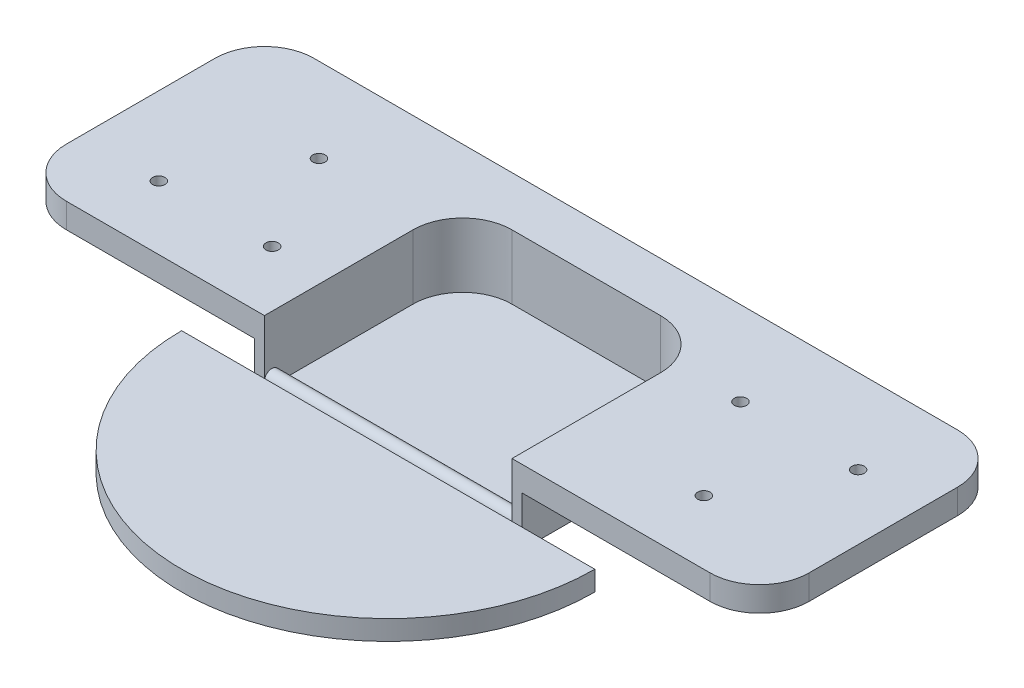
SolidWorks part; units mm, degrees
ref_plane "Front Plane" through (0, 0, 0) normal (0, 0, 1) x (1, 0, 0)
ref_plane "Top Plane" through (0, 0, 0) normal (0, 1, 0) x (1, 0, 0)
ref_plane "Right Plane" through (0, 0, 0) normal (1, 0, 0) x (0, 0, -1)
sketch "Sketch1" plane through (0, 0, 0) normal (0, 1, 0) x (1, 0, 0)
  line L1 (325, -125) -> (-325, -125)
  line L2 (375, -75) -> (375, 75)
  line L3 (325, 125) -> (-325, 125)
  line L4 (-375, -75) -> (-375, 75)
  line L5 (375, -125) -> (-375, 125) construction
  line L6 (375, 125) -> (-375, -125) construction
  arc A0 (325, -125) -> (375, -75) centre (325, -75) ccw
  arc A1 (375, 75) -> (325, 125) centre (325, 75) ccw
  arc A2 (-325, -125) -> (-375, -75) centre (-325, -75) cw
  arc A3 (-325, 125) -> (-375, 75) centre (-325, 75) ccw
  point P0 (0, 0)
  dimension "D3" = 50
  dimension "D1" = 750
  dimension "D2" = 250
extrude "Boss-Extrude1" add sketch "Sketch1" against normal blind 75
sketch "Sketch2" plane through (0, 0, 0) normal (0, 1, 0) x (1, 0, 0)
  line L0 (-325, -125) -> (325, -125) construction
  line L1 (125, -125) -> (-125, -125)
  line L2 (125, -125) -> (125, 25)
  line L3 (75, 75) -> (-75, 75)
  line L4 (-125, -125) -> (-125, 25)
  line L5 (0, 0) -> (125, 0) construction
  arc A0 (125, 25) -> (75, 75) centre (75, 25) ccw
  arc A1 (-75, 75) -> (-125, 25) centre (-75, 25) ccw
  point P11 (125, 75)
  point P14 (-125, 75)
  dimension "D4" = 50
  dimension "D1" = 200
  dimension "D2" = 250
  dimension "D3" = 125
extrude "Cut-Extrude1" cut sketch "Sketch2" against normal blind 65
shell "Shell1" thickness 10 removed face at (0, -75, 0)
sketch "Sketch5" plane through (0, -75, 0) normal (0, -1, 0) x (1, 0, 0)
  line L3 (135, 115) -> (325, 115) construction
  line L4 (325, 125) -> (-325, 125)
  line L5 (-375, 75) -> (-375, -75)
  line L6 (-325, -125) -> (325, -125)
  line L7 (375, -75) -> (375, 75)
  line L8 (325, 125) -> (-325, 125)
  line L9 (-375, 75) -> (-375, -75)
  line L10 (-325, -125) -> (325, -125)
  line L11 (375, -75) -> (375, 75)
  line L12 (365, 75) -> (365, -75) construction
  line L13 (325, -115) -> (-325, -115) construction
  line L14 (-365, -75) -> (-365, 75) construction
  line L15 (-325, 115) -> (-135, 115) construction
  line L19 (135, 115) -> (325, 115)
  line L20 (365, 75) -> (365, -75)
  line L21 (325, -115) -> (-325, -115)
  line L22 (-365, -75) -> (-365, 75)
  line L23 (-325, 115) -> (-135, 115)
  line L24 (135, 115) -> (135, 125)
  line L25 (-135, 115) -> (-135, 125)
  arc A0 (325, -115) -> (365, -75) centre (325, -75) ccw construction
  arc A3 (365, 75) -> (325, 115) centre (325, 75) ccw construction
  arc A4 (375, 75) -> (325, 125) centre (325, 75) ccw
  arc A5 (-325, 125) -> (-375, 75) centre (-325, 75) ccw
  arc A6 (-375, -75) -> (-325, -125) centre (-325, -75) ccw
  arc A7 (325, -125) -> (375, -75) centre (325, -75) ccw
  arc A8 (375, 75) -> (325, 125) centre (325, 75) ccw
  arc A9 (-325, 125) -> (-375, 75) centre (-325, 75) ccw
  arc A10 (-375, -75) -> (-325, -125) centre (-325, -75) ccw
  arc A11 (325, -125) -> (375, -75) centre (325, -75) ccw
  arc A12 (-365, -75) -> (-325, -115) centre (-325, -75) ccw construction
  arc A13 (-325, 115) -> (-365, 75) centre (-325, 75) ccw construction
  arc A14 (325, -115) -> (365, -75) centre (325, -75) ccw
  arc A17 (365, 75) -> (325, 115) centre (325, 75) ccw
  arc A18 (-365, -75) -> (-325, -115) centre (-325, -75) ccw
  arc A19 (-325, 115) -> (-365, 75) centre (-325, 75) ccw
  arc M23 (375, 75) -> (325, 125) centre (325, 75) ccw
  line M24 (325, 125) -> (-325, 125)
  arc M25 (-325, 125) -> (-375, 75) centre (-325, 75) ccw
  line M26 (-375, 75) -> (-375, -75)
  arc M27 (-375, -75) -> (-325, -125) centre (-325, -75) ccw
  line M28 (-325, -125) -> (325, -125)
  arc M29 (325, -125) -> (375, -75) centre (325, -75) ccw
  line M30 (375, -75) -> (375, 75)
  line M36 (135, 115) -> (325, 115)
  arc M37 (325, 115) -> (365, 75) centre (325, 75) cw
  line M38 (365, 75) -> (365, -75)
  arc M39 (365, -75) -> (325, -115) centre (325, -75) cw
  line M40 (325, -115) -> (-325, -115)
  arc M41 (-325, -115) -> (-365, -75) centre (-325, -75) cw
  line M42 (-365, -75) -> (-365, 75)
  arc M43 (-365, 75) -> (-325, 115) centre (-325, 75) cw
  line M44 (-325, 115) -> (-135, 115)
  dimension "D1" = 0
extrude "Cut-Extrude3" cut sketch "Sketch5" against normal blind 50 contours L25 L24 M44 M24 M25 M26 M27 M28 M29 M30 M23 M36 M37 M38 M39 M40 M41 M42 M43 region at (354.7652, -75, 104.7652)
sketch "Sketch6" plane through (0, 0, 0) normal (0, 1, 0) x (1, 0, 0)
  circle A0 centre (-181.6156, -60.6048) radius 6.25
  circle A1 centre (-296.0692, -60.6048) radius 6.25
  circle A2 centre (-234.8683, 39.9395) radius 6.25
  circle A3 centre (190.756, 39.9395) radius 6.25
  circle A4 centre (309.5811, 39.9395) radius 6.25
  circle A5 centre (254.3413, -60.6048) radius 6.25
  dimension "D1" = 12.5
extrude "Cut-Extrude4" cut sketch "Sketch6" against normal blind 10
sketch "Sketch7" plane through (0, -65, 0) normal (0, 1, 0) x (1, 0, 0)
  line L0 (-125, -125) -> (125, -125) construction
  line L4 (-208.6243, -125) -> (208.6243, -125)
  arc A0 (-208.6243, -125) -> (208.6243, -125) centre (0, -125) ccw
extrude "Boss-Extrude2" add sketch "Sketch7" against normal blind 10 and the other way blind 10
sketch "Sketch10" plane through (-125, 0, 0) normal (1, 0, 0) x (0, 0, -1)
  line L2 (-125, -65) -> (-125, -55) construction
  line L3 (25, -65) -> (-125, -65) construction
  circle A0 centre (-117.5, -57.5) radius 7.5
  dimension "D1" = 15
extrude "Boss-Extrude5" add sketch "Sketch10" along normal up to next separate body
